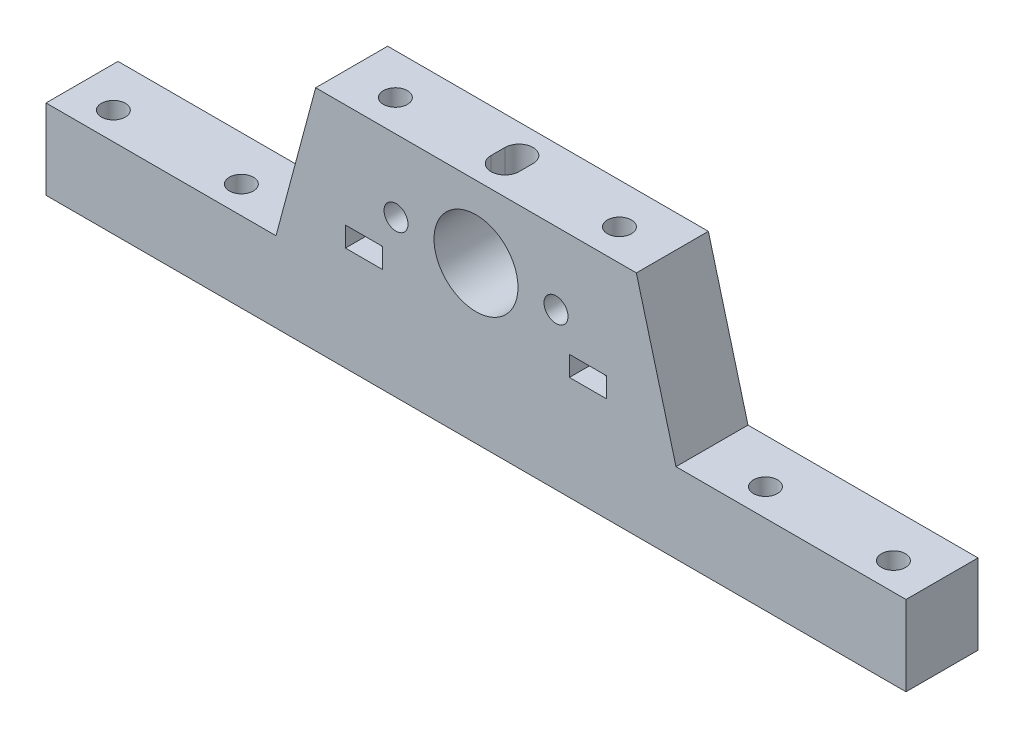
SolidWorks part; units mm, degrees
note: The reader was unsure of these and kept them because the rebuilt part matched: shared geometry of "Sketch1<3>", "Sketch1<6>", "Sketch2<6>", "Sketch1<8>".
ref_plane "Front Plane" through (0, 0, 0) normal (0, 0, 1) x (1, 0, 0)
ref_plane "Top Plane" through (0, 0, 0) normal (0, 1, 0) x (1, 0, 0)
ref_plane "Right Plane" through (0, 0, 0) normal (1, 0, 0) x (0, 0, -1)
sketch "Sketch1" plane through (0, 0, 0) normal (0, 1, 0) x (1, 0, 0)
  line L0 (147.5033, 0) -> (147.5033, -18)
  line L1 (0, 0) -> (215, 0)
  line L2 (0, 0) -> (0, -18)
  line L3 (0, -18) -> (215, -18)
  line L4 (215, 0) -> (215, -18)
  line L5 (67.5033, 0) -> (67.5033, -18)
  line L6 (104.0033, -10.75) -> (104.0033, -7.25)
  line L7 (111.0033, -10.75) -> (111.0033, -7.25)
  line L8 (95.0033, -18) -> (95.0033, 0)
  line L9 (120.0033, -18) -> (120.0033, 0)
  circle A0 centre (9.99, -11.15) radius 3
  circle A1 centre (41.99, -11.15) radius 3
  circle A2 centre (79.5033, -10.15) radius 3
  circle A3 centre (135.5033, -10.15) radius 3
  circle A4 centre (173.0133, -11.15) radius 3
  circle A5 centre (205.0133, -11.15) radius 3
  circle A6 centre (107.5033, -10.75) radius 3.5
  circle A7 centre (107.5033, -7.25) radius 3.5
  dimension "D5" = 6
  dimension "D6" = 6
  dimension "D16" = 7
  dimension "D1" = 215
  dimension "D2" = 18
  dimension "D3" = 11.15
  dimension "D7" = 32
  dimension "D8" = 56
  dimension "D9" = 32
  dimension "D10" = 37.5133
  dimension "D11" = 37.51
  dimension "D12" = 9.99
  dimension "D13" = 9.9867
  dimension "D14" = 80
  dimension "D15" = 12
  dimension "D4" = 10.15
  dimension "D17" = 40
  dimension "D18" = 7.25
  dimension "D19" = 25
  dimension "D20" = 15.5
extrude "Boss-Extrude1" add sketch "Sketch1" along normal blind 20 contours L5 L1 L2 L3 A1 A0 | L4 L1 L0 L3 A5 A4 | L1 L5 L3 L0 A7 L7 A6 L6 A3 A2 | A7 A6 | A6 A7 | A6 A7 | A7 A6 L7 | A7 L6 A6 | L3 L8 L1 L5 A2 | L9 L3 L0 L1 A3
extrude "Boss-Extrude2" add sketch "Sketch1<3>" along normal blind 47 contours L1 L5 L3 L0 A3 A2 | A6 A7 | A6 A7 | A7 A6 | A7 A6 L7 | A7 L6 A6 | L3 L8 L1 L5 A2 | L9 L3 L0 L1 A3
sketch "Sketch1<3>" plane through (0, 0, 0) normal (0, 1, 0) x (1, 0, 0) same geometry as "Sketch1"
ref_plane "Plane1" through (0, 0, 18) normal (0, 0, 1) x (1, 0, 0)
sketch "Sketch2" plane through (0, 0, 18) normal (0, 0, 1) x (1, 0, 0)
  line L0 (147.5033, 47) -> (147.5033, 20) construction
  line L1 (67.5033, 47) -> (147.5033, 47) construction
  line L2 (67.5033, 47) -> (67.5033, 20) construction
  line L3 (140.1533, 31) -> (130.8533, 31)
  line L4 (140.1533, 31) -> (140.1533, 26)
  line L5 (140.1533, 26) -> (130.8533, 26)
  line L6 (130.8533, 31) -> (130.8533, 26)
  line L7 (84.1533, 31) -> (74.8533, 31)
  line L8 (84.1533, 31) -> (84.1533, 26)
  line L9 (84.1533, 26) -> (74.8533, 26)
  line L10 (74.8533, 31) -> (74.8533, 26)
  circle A0 centre (127.5033, 38.99) radius 3
  circle A1 centre (87.5033, 38.99) radius 3
  circle A2 centre (107.5033, 39.05) radius 10.5
  circle A3 centre (87.5033, 38.99) radius 4.475
  circle A4 centre (127.5033, 38.99) radius 4.475
  circle A5 centre (127.5033, 38.99) radius 6.975
  circle A6 centre (87.5033, 38.99) radius 6.975
  dimension "D1" = 6
  dimension "D11" = 21
  dimension "D14" = 8.95
  dimension "D15" = 13.95
  dimension "D2" = 40
  dimension "D3" = 20
  dimension "D4" = 8.01
  dimension "D5" = 9.3
  dimension "D6" = 5
  dimension "D7" = 7.35
  dimension "D8" = 7.35
  dimension "D9" = 16
  dimension "D10" = 40
  dimension "D12" = 7.95
  dimension "D13" = 0.06
extrude "Boss-Extrude3" add sketch "Sketch1<6>" along normal blind 10 from surface contours L3 L9 L1 L8 A7 L7 A6 L6 | L3 L8 L1 L5 A2 | L9 L3 L0 L1 A3
sketch "Sketch1<6>" plane through (0, 0, 0) normal (0, 1, 0) x (1, 0, 0) same geometry as "Sketch1"
extrude "Boss-Extrude4" add sketch "Sketch2" against normal blind 25 contours A3 A1 | A4 A0 | A6 A3 | A5 A4
extrude "Cut-Extrude5" cut sketch "Sketch2<6>" against normal through all contours A2 | A1 | L7 L10 L9 L8 | A0 | L3 L6 L5 L4
sketch "Sketch2<6>" plane through (0, 0, 18) normal (0, 0, 1) x (1, 0, 0) same geometry as "Sketch2"
extrude "Cut-Extrude6" cut sketch "Sketch1<8>" along normal up to surface (57 mm away) contours A3 | A2 up to face at (135.5033, 57, 13.15)
sketch "Sketch1<8>" plane through (0, 0, 0) normal (0, 1, 0) x (1, 0, 0) same geometry as "Sketch1"
chamfer "Chamfer1" distance 10 angle 75 2 edges at (147.5033, 20, 9) (147.5033, 57, 9)
chamfer "Chamfer2" distance 10 angle 75 2 edges at (67.5033, 20, 9) (67.5033, 57, 9)
equation "\"D4@Sketch1\"=\"D3@Sketch1\"-1"
equation "\"D3@Sketch2\"=80/4"
equation "\"D7@Sketch2\"=12-(\"D5@Sketch2\"/2)"
equation "\"D8@Sketch2\"=12-(\"D5@Sketch2\"/2)"
equation "\"D18@Sketch1\"=(\"D2@Sketch1\"-(\"D16@Sketch1\"/2))/2"
equation "\"D20@Sketch1\"=(\"D8@Sketch1\"-\"D19@Sketch1\")/2"
equation "\"D15@Sketch2\"= \"D14@Sketch2\"+5"
